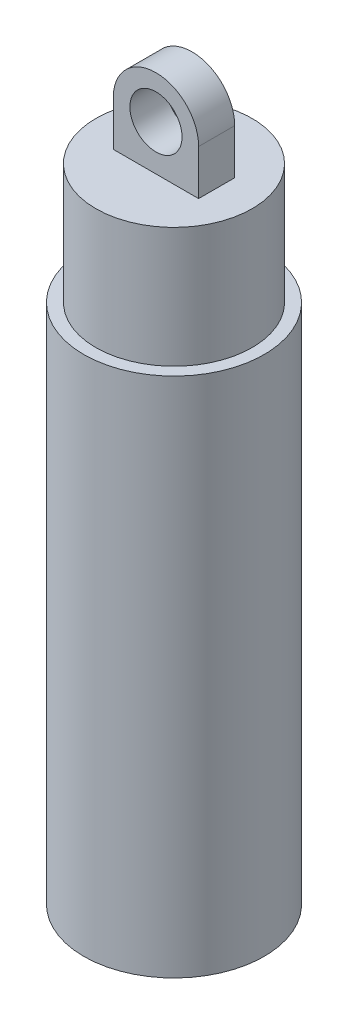
SolidWorks part; units mm, degrees
ref_plane "前视基准面" through (0, 0, 0) normal (0, 0, 1) x (1, 0, 0)
ref_plane "上视基准面" through (0, 0, 0) normal (0, 1, 0) x (1, 0, 0)
ref_plane "右视基准面" through (0, 0, 0) normal (1, 0, 0) x (0, 0, -1)
sketch "草图1" plane through (0, 0, 0) normal (0, 1, 0) x (1, 0, 0)
  circle A0 centre (0, 0) radius 9
  dimension "D1" = 18
extrude "凸台-拉伸1" add sketch "草图1" along normal blind 52
sketch "草图2" plane through (0, 52, 0) normal (0, 1, 0) x (1, 0, 0)
  circle A0 centre (0, 0) radius 7.8
  dimension "D1" = 15.6
extrude "凸台-拉伸2" add sketch "草图2" along normal blind 12
sketch "草图3" plane through (0, 0, 0) normal (0, 0, 1) x (1, 0, 0)
  line L0 (7.8, 64) -> (-7.8, 64) construction
  line L1 (-4.255, 59.5) -> (4.255, 59.5)
  line L2 (-4.255, 59.5) -> (-4.255, 68.5)
  line L4 (4.255, 59.5) -> (4.255, 68.5)
  line L5 (-4.255, 59.5) -> (4.255, 68.5) construction
  line L6 (-4.255, 68.5) -> (4.255, 59.5) construction
  arc A0 (-0.238, 64.2517) -> (0.238, 64.2517) centre (0, 68.5) ccw
  arc A1 (4.255, 68.5) -> (-4.255, 68.5) centre (0, 68.5) ccw
  circle A2 centre (0, 68.5) radius 2.6
  point P0 (0, 64)
  dimension "D2" = 5.2
  dimension "D1" = 8.51
extrude "凸台-拉伸3" add sketch "草图3" along normal blind 1.8 and the other way blind 1.8 contours L4 A1 L2 L1 A2 region at (0, 64.9997, 0)
sketch "草图4" plane through (0, 0, 0) normal (0, 0, 1) x (1, 0, 0)
  line L0 (0, 68.5) -> (0, -16.5) construction
  line L1 (-4.65, -16.5) -> (-4.65, -8.5)
  line L3 (4.65, -8.5) -> (4.65, -16.5)
  line L4 (-4.65, -8.5) -> (-4.65, 0)
  line L5 (-9, 0) -> (9, 0) construction
  line L6 (-4.65, 0) -> (4.65, 0)
  line L7 (4.65, 0) -> (4.65, -8.5)
  circle A0 centre (0, -16.5) radius 1.6
  arc A1 (-4.65, -16.5) -> (4.65, -16.5) centre (0, -16.5) ccw
  dimension "D1" = 3.2
  dimension "D2" = 9.3
extrude "凸台-拉伸4" add sketch "草图4" along normal blind 1.8 and the other way blind 1.8
sketch "草图5" plane through (0, 0, 0) normal (0, -1, 0) x (1, 0, 0)
  circle A0 centre (0, 0) radius 7.5
extrude "切除-拉伸1" cut sketch "草图5" against normal blind 36 and the other way blind 27
